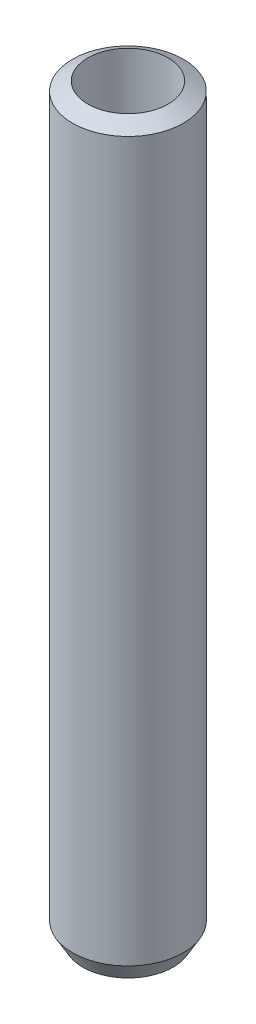
SolidWorks part; units mm, degrees
ref_plane "Front Plane" through (0, 0, 0) normal (0, 0, 1) x (1, 0, 0)
ref_plane "Top Plane" through (0, 0, 0) normal (0, 1, 0) x (1, 0, 0)
ref_plane "Right Plane" through (0, 0, 0) normal (1, 0, 0) x (0, 0, -1)
sketch "Sketch1" plane through (0, 0, 0) normal (0, 1, 0) x (1, 0, 0)
  circle A0 centre (0, 0) radius 25
  dimension "SHAFT_OD" = 50
extrude "Boss-Extrude1" add sketch "Sketch1" along normal blind 336.3835
sketch "Sketch2" plane through (0, 0, 0) normal (0, 1, 0) x (1, 0, 0)
  circle A0 centre (0, 0) radius 18.0814
  dimension "BORE_D" = 36.1627
extrude "Cut-Extrude1" cut sketch "Sketch2" along normal through all
chamfer "Chamfer1" distance 4.5921 angle 60 2 edges at (0, 336.3835, 25) (0, 0, 25) first distance on face at (0, 336.3835, 25) first distance on face at (0, 0, 18.0814)
